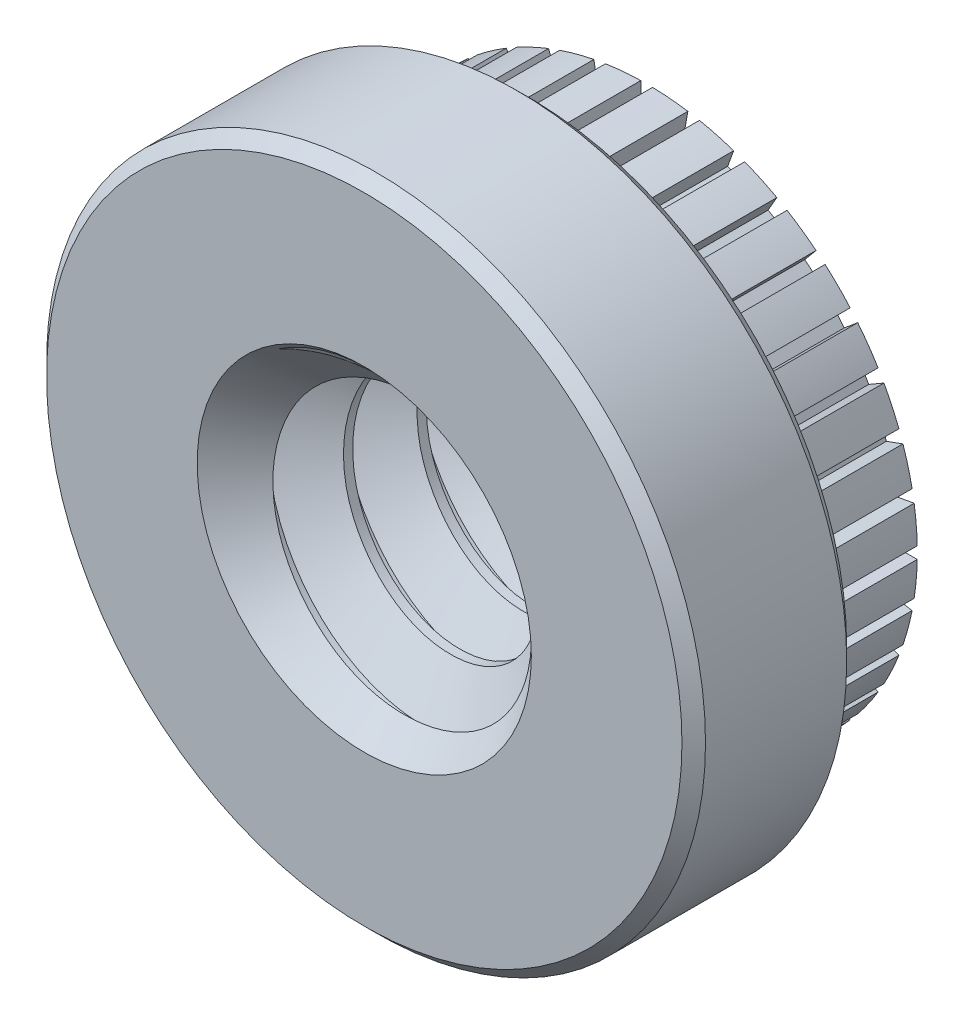
SolidWorks part; units mm, degrees
material "Plain Carbon Steel"
ref_plane "Front Plane" through (0, 0, 0) normal (0, 0, 1) x (1, 0, 0)
ref_plane "Top Plane" through (0, 0, 0) normal (0, 1, 0) x (1, 0, 0)
ref_plane "Right Plane" through (0, 0, 0) normal (1, 0, 0) x (0, 0, -1)
sketch "Sketch1" plane through (0, 0, 0) normal (0, 0, 1) x (1, 0, 0)
  circle A0 centre (0, 0) radius 3.556
  dimension "A" = 7.112
extrude "Extrude1" add sketch "Sketch1" against normal blind 1.778
sketch "Sketch2" plane through (0, 0, -1.778) normal (0, 0, -1) x (-1, 0, 0)
  circle A0 centre (0, 0) radius 2.921
  dimension "C" = 5.842
extrude "Extrude2" add sketch "Sketch2" along normal blind 1.524
sketch "Sketch3" plane through (0, 0, -3.302) normal (0, 0, -1) x (-1, 0, 0)
  line L0 (0, 2.7305) -> (0, 3.556)
  circle A1 centre (0, 0) radius 3.556 construction
  circle A2 centre (0, 0) radius 2.7305
  circle A3 centre (0, 0) radius 2.7305 construction
  dimension "D1" = 0.1905
extrude "Cut-Extrude-Thin1" cut sketch "Sketch3" against normal up to surface (1.524 mm away) thin up to face at (3.556, 0, -1.778) thin type mid plane wall 0.127
pattern_circular "CirPattern1" count 36 over 360 about axis through (0, 0, 0) along (0, 0, 1) of "Cut-Extrude-Thin1"
sketch "Sketch5" plane through (0, 0, -3.302) normal (0, 0, -1) x (-1, 0, 0)
  circle A2 centre (0, 0) radius 2.4765
  circle A3 centre (0, 0) radius 2.4765
  dimension "D1" = 0.254
extrude "Cut-Extrude1" cut sketch "Sketch5" against normal blind 0.254 flip side to cut
chamfer "Chamfer1" distance 0.127 angle 45 1 edges at (-2.4765, 0, -3.302)
sketch "Sketch6" plane through (0, 0, -1.778) normal (0, 0, -1) x (-1, 0, 0)
  circle A0 centre (0, 0) radius 2.4765 construction
  circle A1 centre (0, 0) radius 2.4765
  circle A2 centre (0, 0) radius 3.556 construction
  circle A3 centre (0, 0) radius 3.556
extrude "Cut-Extrude2" cut sketch "Sketch6" along normal blind 0.127
chamfer "Chamfer2" distance 0.127 angle 45 2 edges at (3.556, 0, 0) (3.556, 0, -1.778)
sketch "Sketch7" plane through (0, 0, 0) normal (0, 0, 1) x (1, 0, 0)
  circle A0 centre (0, 0) radius 1.7526
  dimension "Thread Od" = 3.5052
extrude "Cut-Extrude3" cut sketch "Sketch7" against normal through all
sketch "Sketch8" plane through (0, 0, -3.302) normal (0, 0, -1) x (-1, 0, 0)
  circle A0 centre (0, 0) radius 1.7526 construction
  circle A1 centre (0, 0) radius 1.7526
curve "Helix/Spiral1" pitch 0.7937 height 4.953 turns 6.24 parameters "pitch"=0.7937
sketch "Sketch9" plane through (0, 0, 0) normal (1, 0, 0) x (0, 0, -1)
  line L0 (3.9965, 1.7526) -> (3.6989, 1.237)
  line L1 (3.6989, 1.237) -> (3.5997, 1.237)
  line L2 (3.5997, 1.237) -> (3.302, 1.7526)
  line L3 (3.9965, 1.7526) -> (3.302, 1.7526)
  line L4 (3.6493, 1.7526) -> (3.6493, 1.237) construction
  line L5 (3.8477, 1.4948) -> (3.4508, 1.4948) construction
  line L6 (3.302, -1.7526) -> (3.302, 1.7526) construction
  dimension "D1" = 60
  dimension "D2" = 0.0992
sweep "Sweep1" add profiles "Sketch9" path "Helix/Spiral1"
sketch "Sketch10" plane through (0, 0, 0) normal (0, 0, 1) x (1, 0, 0)
  circle A1 centre (0, 0) radius 3.429
  circle A2 centre (0, 0) radius 3.429
  dimension "D1" = 0
extrude "Cut-Extrude4" cut sketch "Sketch10" along normal through all
sketch "Sketch11" plane through (0, 0, -3.302) normal (0, 0, -1) x (-1, 0, 0)
  circle A0 centre (0, 0) radius 2.3495 construction
  circle A1 centre (0, 0) radius 2.3495
extrude "Cut-Extrude5" cut sketch "Sketch11" along normal through all
sketch "Sketch13" plane through (0, 0, 0) normal (0, 0, 1) x (1, 0, 0)
  circle A2 centre (0, 0) radius 1.8034
  circle A3 centre (0, 0) radius 1.8034
  dimension "D1" = 0.0508
extrude "Cut-Extrude6" cut sketch "Sketch13" against normal through all draft 45
sketch "Sketch14" plane through (0, 0, -3.302) normal (0, 0, -1) x (-1, 0, 0)
  circle A2 centre (0, 0) radius 1.8034
  circle A3 centre (0, 0) radius 1.8034
  dimension "D1" = 0.0508
extrude "Cut-Extrude7" cut sketch "Sketch14" against normal through all draft 45
equation "\"D3@Helix/Spiral1\" = \"B@Extrude1\"+.125"
equation "\"D2@Sketch9\" = \"pitch@Helix/Spiral1\"*.125"
equation "\"D3@Sketch9\" = \"pitch@Helix/Spiral1\"*.50"
